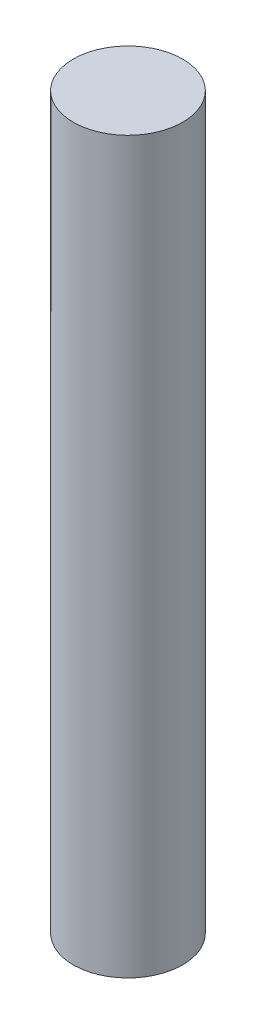
SolidWorks part; units mm, degrees
material "1060 Alloy"
ref_plane "Front Plane" through (0, 0, 0) normal (0, 0, 1) x (1, 0, 0)
ref_plane "Top Plane" through (0, 0, 0) normal (0, 1, 0) x (1, 0, 0)
ref_plane "Right Plane" through (0, 0, 0) normal (1, 0, 0) x (0, 0, -1)
sketch "Sketch1" plane through (0, 0, 0) normal (0, 0, 1) x (1, 0, 0)
  line L0 (0, 101.6) -> (0, -101.6) construction
  line L1 (0, 63.5) -> (9.525, 63.5)
  line L2 (9.525, 63.5) -> (9.525, -63.5)
  line L3 (9.525, -63.5) -> (0, -63.5)
  line L4 (0, 63.5) -> (0, -63.5)
  point P5 (9.525, 0)
  dimension "D1" = 127
  dimension "D2" = 19.05
revolve "Revolve1" add sketch "Sketch1" angle 360 about L0
equation "\"Rod Diameter\"= 0.75in'This will remain constant in the steering column"
equation "\"Rod Length\"= 5in'This might change for different rods in steering column"
equation "\"D1@Sketch1\"= \"Rod Length\""
equation "\"D2@Sketch1\"=\"Rod Diameter\""
